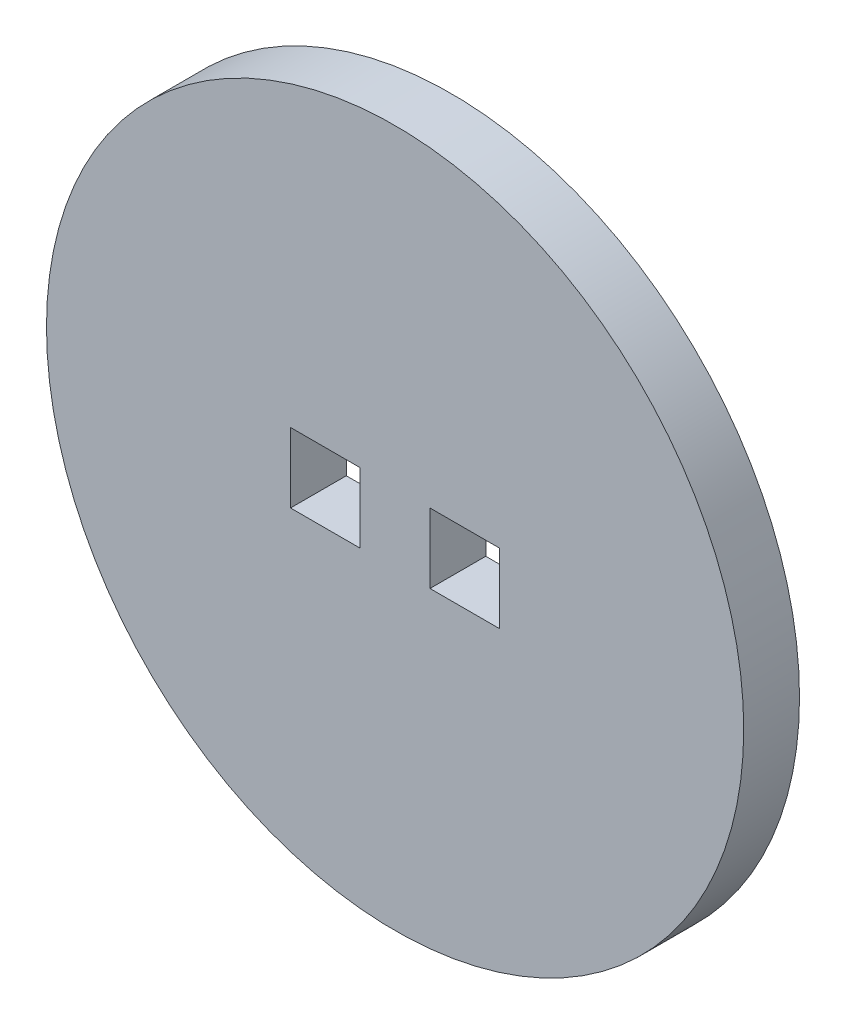
SolidWorks part; units mm, degrees
ref_plane "Front Plane" through (0, 0, 0) normal (0, 0, 1) x (1, 0, 0)
ref_plane "Top Plane" through (0, 0, 0) normal (0, 1, 0) x (1, 0, 0)
ref_plane "Right Plane" through (0, 0, 0) normal (1, 0, 0) x (0, 0, -1)
sketch "Sketch1" plane through (0, 0, 0) normal (0, 0, 1) x (1, 0, 0)
  line L1 (1.5875, -1.5875) -> (4.7625, -1.5875)
  line L2 (1.5875, -1.5875) -> (1.5875, 1.5875)
  line L3 (1.5875, 1.5875) -> (4.7625, 1.5875)
  line L4 (4.7625, -1.5875) -> (4.7625, 1.5875)
  line L5 (1.5875, -1.5875) -> (4.7625, 1.5875) construction
  line L6 (1.5875, 1.5875) -> (4.7625, -1.5875) construction
  line L7 (-4.7625, -1.5875) -> (-1.5875, -1.5875)
  line L8 (-4.7625, -1.5875) -> (-4.7625, 1.5875)
  line L9 (-4.7625, 1.5875) -> (-1.5875, 1.5875)
  line L10 (-1.5875, -1.5875) -> (-1.5875, 1.5875)
  line L11 (-4.7625, -1.5875) -> (-1.5875, 1.5875) construction
  line L12 (-4.7625, 1.5875) -> (-1.5875, -1.5875) construction
  circle A0 centre (0, 0) radius 15.875
  point P3 (3.175, 0)
  point P8 (-3.175, 0)
  point P13 (0, 0)
  point P14 (0, 0)
  point P15 (4.9256, -1.5875)
  dimension "D1" = 31.75
  dimension "D2" = 3.175
  dimension "D3" = 3.175
  dimension "D4" = 1.5875
extrude "Boss-Extrude1" add sketch "Sketch1" along normal blind 2.54 contours L1 L4 L3 L2 | L7 L10 L9 L8 | A0 region at (3.175, 0, 0) region at (-3.175, 0, 0)
